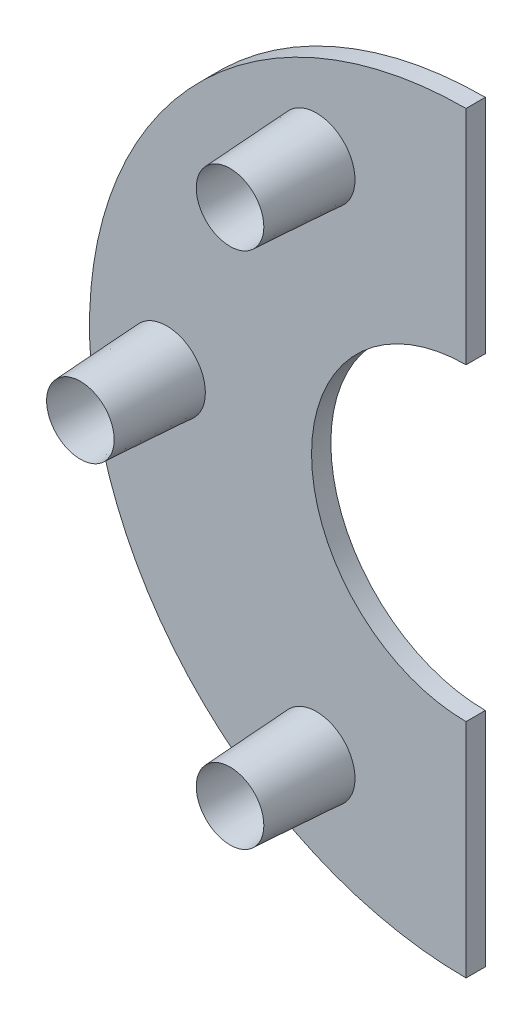
SolidWorks part; units mm, degrees
ref_plane "정면" through (0, 0, 0) normal (0, 0, 1) x (1, 0, 0)
ref_plane "윗면" through (0, 0, 0) normal (0, 1, 0) x (1, 0, 0)
ref_plane "우측면" through (0, 0, 0) normal (1, 0, 0) x (0, 0, -1)
sketch "스케치1" plane through (0, 0, 0) normal (0, 0, 1) x (1, 0, 0)
  line L0 (0, 1.95) -> (0, -1.95)
  arc A0 (0, 0.8) -> (0, -0.8) centre (0, 0) ccw
  arc A1 (0, 1.95) -> (0, -1.95) centre (0, 0) ccw
  dimension "D1" = 3.9
  dimension "D2" = 1.6
extrude "보스-돌출1" add sketch "스케치1" along normal blind 0.1 contours L0 A1 A0 region at (-0.9264, 0, 0)
sketch "스케치2" plane through (0, 0, 0.1) normal (0, 0, 1) x (1, 0, 0)
  line L0 (0, 0) -> (-1.0544, 1.8262) construction
  line L1 (0, 0) -> (-2.6169, 0) construction
  line L2 (0, 0) -> (-1.1955, -2.0707) construction
  circle A0 centre (0, 0) radius 1.75
  arc A1 (0, 1.95) -> (0, -1.95) centre (0, 0) ccw construction
  circle A2 centre (-0.775, -1.3423) radius 0.2
  circle A3 centre (-0.775, -1.3423) radius 0.15
  circle A4 centre (-1.55, 0) radius 0.2
  circle A5 centre (-1.55, 0) radius 0.15
  circle A6 centre (-0.775, 1.3423) radius 0.2
  circle A7 centre (-0.775, 1.3423) radius 0.15
  point P16 (0, 0)
  point P17 (0, 0)
  point P23 (0, 0)
  dimension "D1" = 0.2
  dimension "D4" = 0.4
  dimension "D5" = 0.3
  dimension "D2" = 60
  dimension "D3" = 60
  dimension "D6" = 3
extrude "보스-돌출3" add sketch "스케치2" along normal blind 0.5 draft 3.2 contours A2 A3 | A6 A7 | A4 | A5 region at (-0.6778, 1.5106, 0.1) region at (-0.8722, -1.174, 0.1)
sketch "스케치3" plane through (0, 0, 0.1) normal (0, 0, 1) x (1, 0, 0)
  circle A0 centre (-0.775, -1.3423) radius 0.15 construction
  circle A1 centre (-0.775, 1.3423) radius 0.15
  circle A2 centre (-0.775, 1.3423) radius 0.15
  circle A3 centre (-1.55, 0) radius 0.15 construction
  circle A4 centre (-0.775, -1.3423) radius 0.15
  circle A5 centre (-1.55, 0) radius 0.15
  dimension "D1" = 0
extrude "컷-돌출1" cut sketch "스케치3" against normal through all
